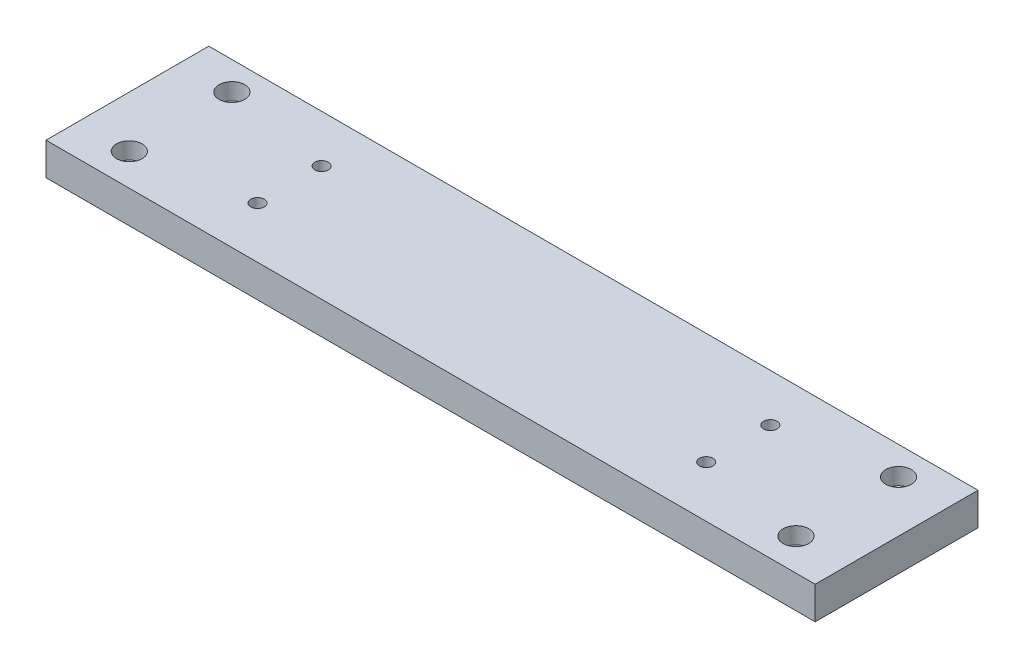
SolidWorks part; units mm, degrees
ref_plane "Front Plane" through (0, 0, 0) normal (0, 0, 1) x (1, 0, 0)
ref_plane "Top Plane" through (0, 0, 0) normal (0, 1, 0) x (1, 0, 0)
ref_plane "Right Plane" through (0, 0, 0) normal (1, 0, 0) x (0, 0, -1)
sketch "Sketch1" plane through (0, 0, 0) normal (0, 1, 0) x (1, 0, 0)
  line L1 (0, 0) -> (600, 0)
  line L2 (0, 0) -> (0, 127)
  line L3 (0, 127) -> (600, 127)
  line L4 (600, 0) -> (600, 127)
  dimension "D1" = 600
  dimension "D2" = 127
extrude "Boss-Extrude1" add sketch "Sketch1" along normal blind 25.4
sketch "Sketch2" plane through (0, 25.4, 0) normal (0, 1, 0) x (1, 0, 0)
  line L1 (0, 0) -> (300, 0)
  line L2 (0, 0) -> (0, 65)
  line L3 (0, 65) -> (300, 65)
  line L4 (300, 0) -> (300, 65)
  line L5 (40, 105) -> (560, 105)
  line L6 (40, 105) -> (40, 25)
  line L7 (40, 25) -> (560, 25)
  line L8 (560, 105) -> (560, 25)
  line L9 (40, 105) -> (560, 25) construction
  line L10 (40, 25) -> (560, 105) construction
  circle A0 centre (40, 105) radius 6
  circle A1 centre (40, 25) radius 6
  circle A2 centre (560, 25) radius 6
  circle A3 centre (560, 105) radius 6
  dimension "D1" = 300
  dimension "D2" = 65
  dimension "D3" = 520
  dimension "D4" = 80
extrude "Cut-Extrude1" cut sketch "Sketch2" against normal blind 25.4 contours A2 | A3 | A1 | A0
sketch "Sketch3" plane through (0, 25.4, 0) normal (0, 1, 0) x (1, 0, 0)
  line L1 (0, 0) -> (300, 0)
  line L2 (0, 0) -> (0, 65)
  line L3 (0, 65) -> (300, 65)
  line L4 (300, 0) -> (300, 65)
  line L5 (125, 90) -> (475, 90)
  line L6 (125, 90) -> (125, 40)
  line L7 (125, 40) -> (475, 40)
  line L8 (475, 90) -> (475, 40)
  line L9 (125, 90) -> (475, 40) construction
  line L10 (125, 40) -> (475, 90) construction
  circle A0 centre (125, 90) radius 5.25
  circle A1 centre (125, 40) radius 5.25
  circle A2 centre (475, 40) radius 5.25
  circle A3 centre (475, 90) radius 5.25
  dimension "D1" = 300
  dimension "D2" = 65
  dimension "D3" = 350
  dimension "D4" = 50
extrude "Cut-Extrude2" cut sketch "Sketch3" against normal blind 25.4 contours A0 | A1 | A2 | A3
sketch "Sketch4" plane through (0, 25.4, 0) normal (0, 1, 0) x (1, 0, 0)
  circle A1 centre (40, 105) radius 10
  circle A2 centre (40, 25) radius 10
  circle A3 centre (560, 25) radius 10
  circle A4 centre (560, 105) radius 10
extrude "Cut-Extrude3" cut sketch "Sketch4" against normal blind 13
